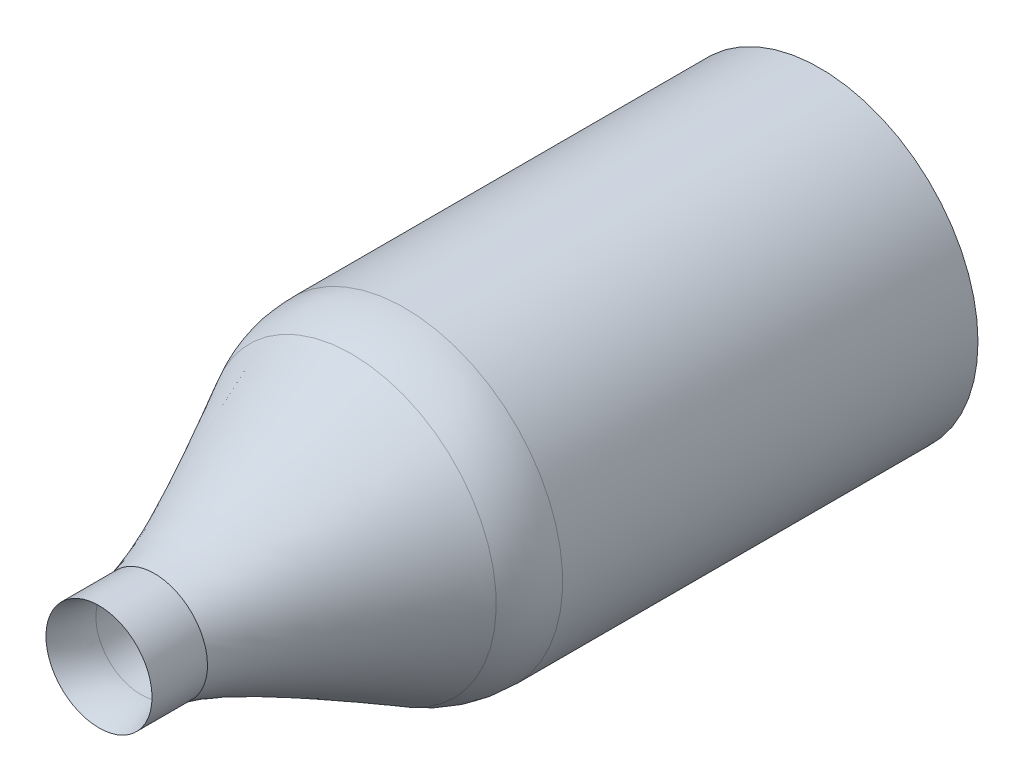
SolidWorks part; units mm, degrees
ref_plane "Front Plane" through (0, 0, 0) normal (0, 0, 1) x (1, 0, 0)
ref_plane "Top Plane" through (0, 0, 0) normal (0, 1, 0) x (1, 0, 0)
ref_plane "Right Plane" through (0, 0, 0) normal (1, 0, 0) x (0, 0, -1)
sketch "Sketch1" plane through (0, 0, 0) normal (0, 0, 1) x (1, 0, 0)
  circle A0 centre (0, 0) radius 14.25
  dimension "D1" = 28.5
extrude "Extrude-Thin1" add sketch "Sketch1" along normal blind 40 thin thin type one direction reverse wall 0.5
ref_plane "Plane1" through (0, 0, 60) normal (0, 0, 1) x (1, 0, 0)
sketch "Sketch2" plane through (0, 0, 60) normal (0, 0, 1) x (1, 0, 0)
  circle A0 centre (0, 0) radius 4.7807
extrude "Boss-Extrude1" add sketch "Sketch2" along normal blind 5 separate body
loft "Loft1" add section edge at (14.25, 0, 40) section edge at (4.7807, 0, 60) connector at (-8.0393, 11.7657, 40) connector at (-4.7219, 0.7479, 60)
sketch "Sketch3" plane through (0, 0, 65) normal (0, 0, 1) x (1, 0, 0)
  circle A0 centre (0, 0) radius 4.0453
extrude "Cut-Extrude1" cut sketch "Sketch3" against normal blind 43
fillet "Fillet1" radius 10 1 edges at (14.25, 0, 40)
fillet "Fillet2" radius 10 1 edges at (4.0453, 0, 40)
fillet "Fillet3" radius 10 1 edges at (4.0453, 0, 65)
fillet "Fillet4" radius 10 1 edges at (13.75, 0, 0)
